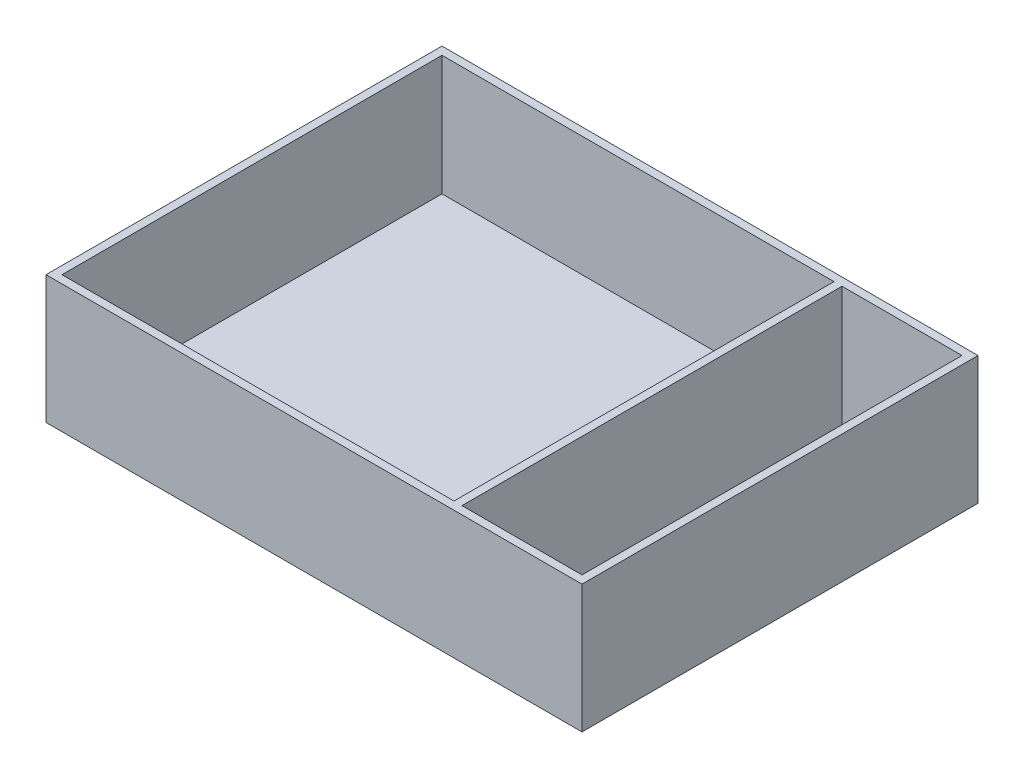
SolidWorks part; units mm, degrees
ref_plane "Alzado" through (0, 0, 0) normal (0, 0, 1) x (1, 0, 0)
ref_plane "Planta" through (0, 0, 0) normal (0, 1, 0) x (1, 0, 0)
ref_plane "Vista lateral" through (0, 0, 0) normal (1, 0, 0) x (0, 0, -1)
sketch "Croquis1" plane through (0, 0, 0) normal (0, 1, 0) x (1, 0, 0)
  line L1 (-130, -95) -> (130, -95)
  line L2 (-130, -95) -> (-130, 95)
  line L3 (-130, 95) -> (130, 95)
  line L4 (130, -95) -> (130, 95)
  line L5 (-130, -95) -> (130, 95) construction
  line L6 (-130, 95) -> (130, -95) construction
  line L7 (-134, -99) -> (134, -99)
  line L8 (-134, -99) -> (-134, 99)
  line L9 (-134, 99) -> (134, 99)
  line L10 (134, -99) -> (134, 99)
  line L11 (-134, -99) -> (134, 99) construction
  line L12 (-134, 99) -> (134, -99) construction
  point P0 (0, 0)
  point P5 (0, 0)
  dimension "D1" = 190
  dimension "D2" = 260
  dimension "D3" = 4
  dimension "D4" = 4
extrude "Saliente-Extruir1" add sketch "Croquis1" along normal blind 60
sketch "Croquis3" plane through (0, 0, 0) normal (0, -1, 0) x (1, 0, 0)
  line L1 (-134, 99) -> (134, 99)
  line L2 (-134, 99) -> (-134, -99)
  line L3 (-134, -99) -> (134, -99)
  line L4 (134, 99) -> (134, -99)
extrude "Saliente-Extruir2" add sketch "Croquis3" along normal blind 4
sketch "Croquis4" plane through (0, 0, 0) normal (0, 1, 0) x (1, 0, 0)
  line L0 (130, 95) -> (-130, 95) construction
  line L1 (70, 95) -> (66, 95)
  line L2 (70, 95) -> (70, -95)
  line L3 (70, -95) -> (66, -95)
  line L4 (66, 95) -> (66, -95)
  line L5 (-130, -95) -> (130, -95) construction
  line L6 (130, -95) -> (130, 95) construction
  dimension "D1" = 4
  dimension "D2" = 60
extrude "Saliente-Extruir3" add sketch "Croquis4" along normal blind 60
